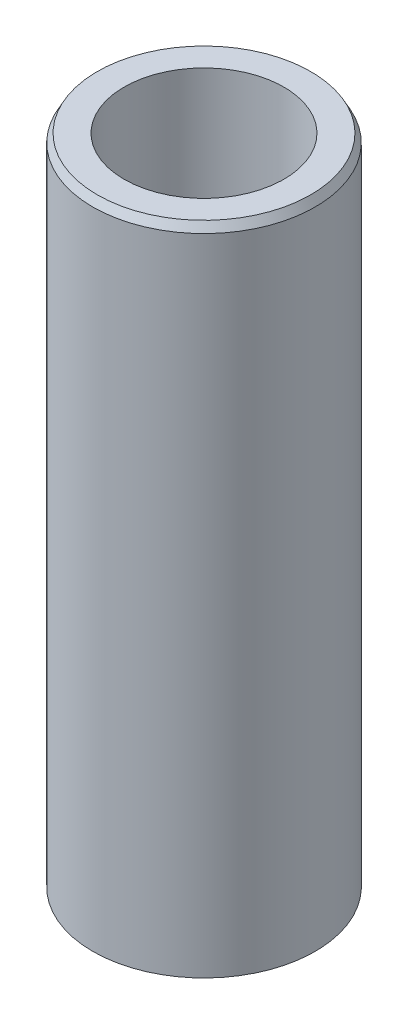
SolidWorks part; units mm, degrees
ref_plane "Front Plane" through (0, 0, 0) normal (0, 0, 1) x (1, 0, 0)
ref_plane "Top Plane" through (0, 0, 0) normal (0, 1, 0) x (1, 0, 0)
ref_plane "Right Plane" through (0, 0, 0) normal (1, 0, 0) x (0, 0, -1)
sketch "Sketch1" plane through (0, 0, 0) normal (0, 1, 0) x (1, 0, 0)
  circle A0 centre (0, 0) radius 57.5
  dimension "SHAFT_OD" = 115
extrude "Boss-Extrude1" add sketch "Sketch1" along normal blind 339.8876
sketch "Sketch2" plane through (0, 0, 0) normal (0, 1, 0) x (1, 0, 0)
  circle A0 centre (0, 0) radius 41.3139
  dimension "BORE_D" = 82.6278
extrude "Cut-Extrude1" cut sketch "Sketch2" along normal through all
chamfer "Chamfer1" distance 4.3058 angle 28.192 2 edges at (0, 339.8876, 57.5) (0, 0, 57.5) first distance on face at (0, 339.8876, 57.5) first distance on face at (0, 0, 41.3139)
